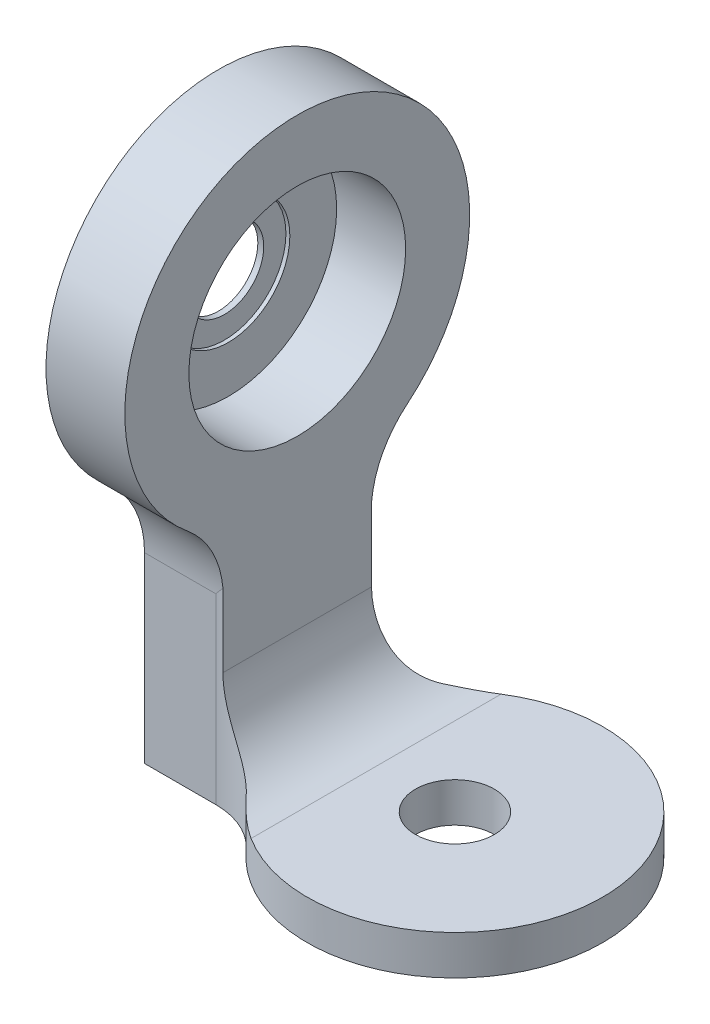
SolidWorks part; units mm, degrees
ref_plane "Front" through (0, 0, 0) normal (0, 0, 1) x (1, 0, 0)
ref_plane "Top" through (0, 0, 0) normal (0, 1, 0) x (1, 0, 0)
ref_plane "Right" through (0, 0, 0) normal (1, 0, 0) x (0, 0, -1)
sketch "草圖1" plane through (0, 0, 0) normal (0, 1, 0) x (1, 0, 0)
  line L0 (-35.8566, 0) -> (35.8566, 0) construction
  line L1 (-24, 7.5) -> (-12.9904, 7.5)
  line L2 (-24, -7.5) -> (-12.9904, -7.5)
  line L3 (-24, 7.5) -> (-24, -7.5)
  circle A0 centre (0, 0) radius 4
  circle A1 centre (0, 0) radius 15
  point P0 (0, 0)
  point P11 (-13.3079, 6.921)
  point P24 (0, 0)
  dimension "D1" = 8
  dimension "D2" = 30
  dimension "D3" = 24
  dimension "D4" = 15
extrude "填料-伸長1" add sketch "草圖1" along normal blind 4 contours L0 L3 L2 A1 | L3 L0 A1 L1 | A1 L0 A0 | L0 A1 A0 region at (0, 0, -6.7236) region at (0, 0, 6.7236) region at (-19.1564, 0, -3.8782) region at (-19.1564, 0, 3.8782)
sketch "草圖2" plane through (0, 4, 0) normal (0, 1, 0) x (1, 0, 0)
  line L1 (-24, 7.5) -> (-17, 7.5)
  line L2 (-24, 7.5) -> (-24, -7.5)
  line L3 (-24, -7.5) -> (-17, -7.5)
  line L4 (-17, 7.5) -> (-17, -7.5)
  line L5 (-26.5539, 0) -> (26.5539, 0) construction
  line L6 (-24, 7.5) -> (-24, -7.5) construction
  line L7 (-24, 7.5) -> (-12.9904, 7.5) construction
  point P7 (-27.1382, 6.9718)
  point P8 (-24, 0)
  point P13 (0, 0)
  dimension "D1" = 7
sketch "草圖4" plane through (-24, 0, 0) normal (-1, 0, 0) x (0, 0, 1)
  line L0 (0, -21.9207) -> (0, 21.9207) construction
  line L4 (-7.5, 23.931) -> (-7.5, 4)
  line L5 (-7.5, 4) -> (7.5, 4)
  line L6 (7.5, 23.931) -> (7.5, 4)
  line L7 (0, 4) -> (0, 39.7424) construction
  line L8 (-7.5, 13.9655) -> (7.5, 13.9655) construction
  circle A0 centre (0, 39.7424) radius 17.5
  point P1 (0, 13.9655)
  point P5 (0, 0)
  point P10 (6.921, 23.931)
  point P11 (0, 42.2693)
  line M4 (7.5, 4) -> (-7.5, 4)
  dimension "D1" = 35
extrude "填料-伸長2" add sketch "草圖4" against normal blind 8 contours A0 | A0 L4 L6 M4 region at (-24, 13.4036, 0) region at (-24, 39.7424, 0)
sketch "草圖3" plane through (-16, 0, 0) normal (-1, 0, 0) x (0, 0, 1)
  line L0 (0, 11.9988) -> (0, -11.9988) construction
  circle A0 centre (0, 40) radius 11
  point P6 (0, 0)
  dimension "D1" = 22
  dimension "D2" = 40
extrude "除料-伸長1" cut sketch "草圖3" along normal blind 7
fillet "圓角5" radius 7.5 2 edges at (-12.9904, 2, 7.5) (-12.9904, 2, -7.5)
fillet "圓角6" radius 10 2 edges at (-20.3853, 23.931, -7.5) (-20.3853, 23.931, 7.5)
fillet "圓角7" radius 8 1 edges at (-16, 4, 0)
sketch "草圖5" plane through (-23, 0, 0) normal (1, 0, 0) x (0, 0, -1)
  circle A0 centre (0, 40) radius 4
  dimension "D1" = 8
extrude "除料-伸長2" cut sketch "草圖5" against normal through all
sketch "草圖6" plane through (-23, 0, 0) normal (1, 0, 0) x (0, 0, -1)
  circle A0 centre (0, 40) radius 6.25
  dimension "D1" = 12.5
extrude "除料-伸長3" cut sketch "草圖6" against normal blind 0.4
